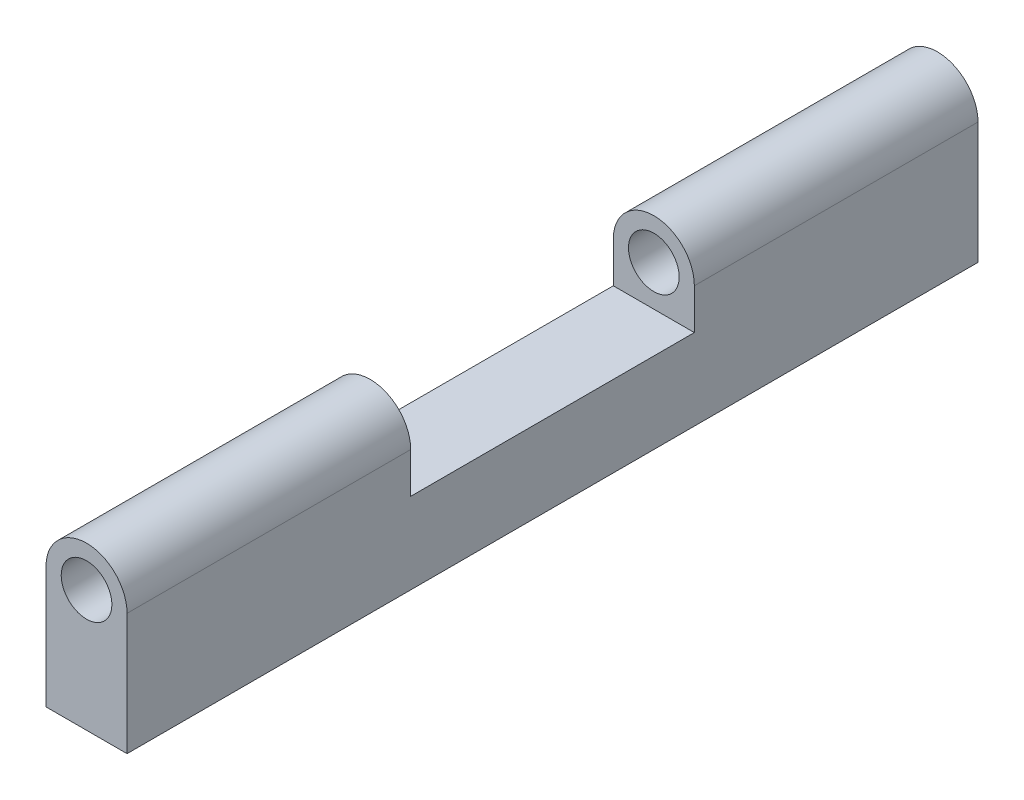
SolidWorks part; units mm, degrees
ref_plane "Front Plane" through (0, 0, 0) normal (0, 0, 1) x (1, 0, 0)
ref_plane "Top Plane" through (0, 0, 0) normal (0, 1, 0) x (1, 0, 0)
ref_plane "Right Plane" through (0, 0, 0) normal (1, 0, 0) x (0, 0, -1)
sketch "Sketch1" plane through (0, 0, 0) normal (0, 0, 1) x (1, 0, 0)
  line L0 (-2, 2.8712) -> (-2, -3.1288)
  line L1 (-2, -3.1288) -> (2, -3.1288)
  line L2 (2, -3.1288) -> (2, 2.8712)
  circle A0 centre (0, 2.8712) radius 1.25
  arc A1 (-2, 2.8712) -> (2, 2.8712) centre (0, 2.8712) cw
  point P7 (0, -3.1288)
  dimension "D1" = 2.5
  dimension "D2" = 4
  dimension "D3" = 6
extrude "Boss-Extrude1" add sketch "Sketch1" along normal blind 42
sketch "Sketch2" plane through (0, 0, 0) normal (1, 0, 0) x (0, 0, -1)
  line L0 (0, 4.8712) -> (-42, 4.8712) construction
  line L1 (-14, 4.8712) -> (-28, 4.8712)
  line L2 (-14, 4.8712) -> (-14, 0.8712)
  line L3 (-14, 0.8712) -> (-28, 0.8712)
  line L4 (-28, 4.8712) -> (-28, 0.8712)
  line L5 (-42, 4.8712) -> (0, 4.8712) construction
  point P6 (-21, 4.8712)
  point P11 (-21, 4.8712)
  dimension "D1" = 14
  dimension "D2" = 4
extrude "Cut-Extrude1" cut sketch "Sketch2" against normal through all both and the other way through all
equation "\"0.510.00mm\"=785.398"
